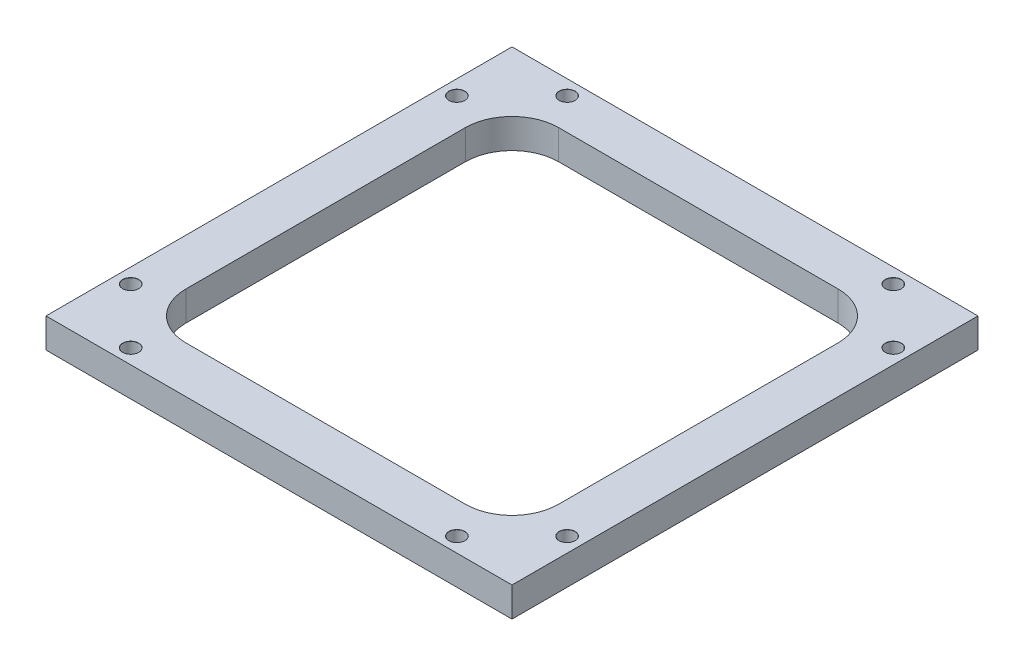
SolidWorks part; units mm, degrees
material "6061 Alloy"
ref_plane "Front Plane" through (0, 0, 0) normal (0, 0, 1) x (1, 0, 0)
ref_plane "Top Plane" through (0, 0, 0) normal (0, 1, 0) x (1, 0, 0)
ref_plane "Right Plane" through (0, 0, 0) normal (1, 0, 0) x (0, 0, -1)
sketch "Sketch1" plane through (0, 0, 0) normal (0, 1, 0) x (1, 0, 0)
  line L1 (-50, -50) -> (50, -50)
  line L2 (-50, -50) -> (-50, 50)
  line L3 (-50, 50) -> (50, 50)
  line L4 (50, -50) -> (50, 50)
  line L5 (-50, -50) -> (50, 50) construction
  line L6 (-50, 50) -> (50, -50) construction
extrude "Boss-Extrude3" add sketch "Sketch1" along normal blind 6.35 contours L1 L4 L3 L2 region at (0, 0, 0)
sketch "Sketch8" plane through (0, 6.35, 0) normal (0, 1, 0) x (1, 0, 0)
  line L0 (-50, -50) -> (-39.5, -50)
  line L1 (-50, -50) -> (50, -50) construction
  line L2 (-39.5, -50) -> (-39.5, -39.5)
  line L3 (50, -50) -> (39.5, -50)
  line L4 (39.5, -50) -> (39.5, -39.5)
  line L5 (50, 50) -> (39.5, 50)
  line L6 (-50, 50) -> (50, 50) construction
  line L7 (39.5, 50) -> (39.5, 39.5)
  line L8 (-50, 50) -> (-39.5, 50)
  line L9 (-50, -50) -> (-50, 50) construction
  line L10 (-39.5, 50) -> (-39.5, 39.5)
sketch "Sketch13" plane through (0, 6.35, 0) normal (0, 1, 0) x (1, 0, 0)
  line L1 (-50, -50) -> (-35, -50)
  line L2 (-50, -50) -> (50, -50) construction
  line L3 (-35, -50) -> (-35, -46.825)
  line L4 (-50, -50) -> (-50, -35)
  line L5 (-50, -50) -> (-50, 50) construction
  line L6 (-50, -35) -> (-46.825, -35)
  line L7 (-50, 50) -> (-35, 50)
  line L8 (-50, 50) -> (50, 50) construction
  line L9 (-35, 50) -> (-35, 46.825)
  line L10 (-50, 50) -> (-50, 35)
  line L11 (-50, 35) -> (-46.825, 35)
  line L13 (50, 50) -> (35, 50)
  line L14 (35, 50) -> (35, 46.825)
  line L15 (50, 50) -> (50, 35)
  line L16 (50, -50) -> (50, 50) construction
  line L17 (50, 35) -> (46.825, 35)
  line L18 (50, -50) -> (50, -35)
  line L19 (50, -35) -> (46.825, -35)
  line L20 (50, -50) -> (35, -50)
  line L21 (35, -50) -> (35, -46.825)
hole_wizard "M3 Clearance Hole1" positions "Sketch17" profile "Sketch18" hole size "M3" standard "ANSI Metric" end condition through all
sketch "Sketch17" plane through (0, 6.35, 0) normal (0, 1, 0) x (1, 0, 0)
  point P0 (-46.825, 35)
  point P3 (-35, 46.825)
  point P6 (35, 46.825)
  point P9 (46.825, 35)
  point P12 (46.825, -35)
  point P15 (35, -46.825)
  point P18 (-35, -46.825)
  point P21 (-46.825, -35)
sketch "Sketch18" plane through (-46.825, 6.35, -35) normal (1, 0, 0) x (0, 0, 1)
  line L0 (0, 0) -> (0, 6.35)
  line L1 (0, 6.35) -> (1.7, 6.35)
  line L2 (1.7, 6.35) -> (1.7, 0.025)
  line L3 (1.7, 0.025) -> (1.725, 0)
  line L5 (1.725, 0) -> (0, 0)
  line L6 (-1.7, 0.025) -> (-1.725, 0) construction
  line L11 (0, -6.35) -> (0, 107.95) construction
  dimension "Thru Hole Dia." = 3.4
  dimension "Thru Hole Depth" = 6.35
  dimension "Near C'Sink Dia." = 3.45
  dimension "Near C'Sink Angle" = 90
sketch "Sketch19" plane through (0, 6.35, 0) normal (0, 1, 0) x (1, 0, 0)
  line L1 (-30, -40) -> (30, -40)
  line L2 (-40, -30) -> (-40, 30)
  line L3 (-30, 40) -> (30, 40)
  line L4 (40, -30) -> (40, 30)
  line L5 (-40, -40) -> (40, 40) construction
  line L6 (-40, 40) -> (40, -40) construction
  arc A0 (-30, -40) -> (-40, -30) centre (-30, -30) cw
  arc A1 (40, -30) -> (30, -40) centre (30, -30) cw
  arc A2 (30, 40) -> (40, 30) centre (30, 30) cw
  arc A3 (-30, 40) -> (-40, 30) centre (-30, 30) ccw
  point P0 (0, 0)
  dimension "D1" = 10
extrude "Cut-Extrude1" cut sketch "Sketch19" against normal blind 10
